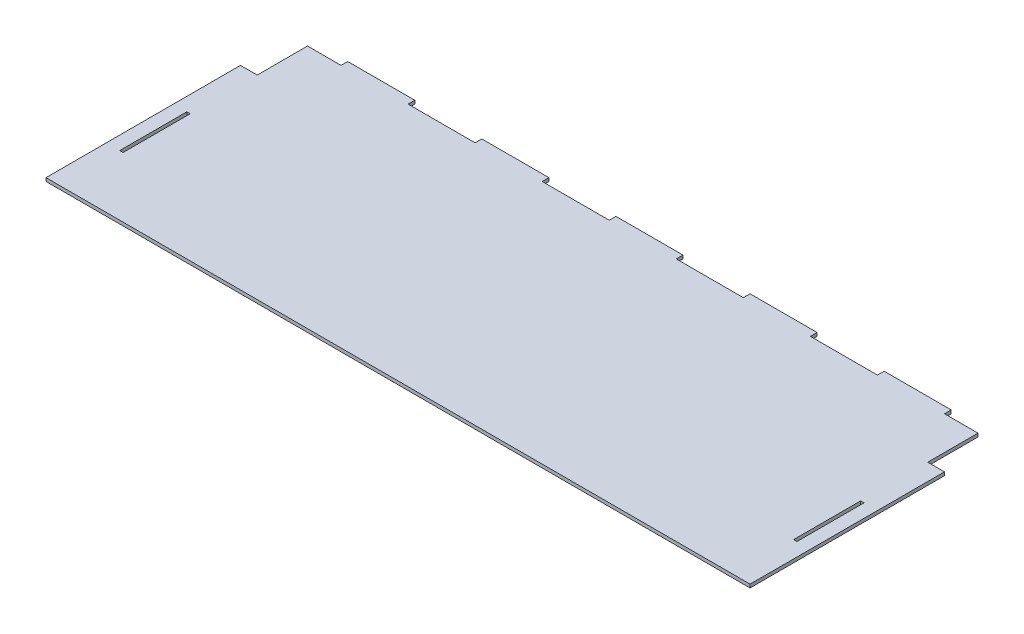
SolidWorks part; units mm, degrees
ref_plane "Přední rovina" through (0, 0, 0) normal (0, 0, 1) x (1, 0, 0)
ref_plane "Horní rovina" through (0, 0, 0) normal (0, 1, 0) x (1, 0, 0)
ref_plane "Pravá rovina" through (0, 0, 0) normal (1, 0, 0) x (0, 0, -1)
sketch "Skica1" plane through (0, 0, 0) normal (0, 1, 0) x (1, 0, 0)
  line L0 (100, 0) -> (100, 43.3055)
  line L5 (0, 0) -> (200, 0)
  line L6 (0, 0) -> (0, 73)
  line L7 (0, 73) -> (200, 73)
  line L8 (200, 0) -> (200, 73)
  line L9 (0, 58) -> (-5, 58)
  line L10 (0, 58) -> (0, 0)
  line L11 (0, 0) -> (-5, 0)
  line L12 (-5, 58) -> (-5, 0)
  line L13 (0, 38) -> (-1, 38)
  line L14 (0, 38) -> (0, 18)
  line L15 (0, 18) -> (-1, 18)
  line L16 (-1, 38) -> (-1, 18)
  line L17 (200, 18) -> (201, 18)
  line L18 (201, 38) -> (201, 18)
  line L19 (200, 38) -> (201, 38)
  line L20 (200, 38) -> (200, 18)
  line L21 (200, 0) -> (205, 0)
  line L22 (205, 58) -> (205, 0)
  line L23 (200, 58) -> (205, 58)
  line L24 (200, 58) -> (200, 0)
  line L25 (0, 0) -> (-5, 0)
  line L26 (10, 73) -> (30, 73)
  line L27 (10, 73) -> (10, 75)
  line L28 (10, 75) -> (30, 75)
  line L29 (30, 73) -> (30, 75)
  line L30 (50, 73) -> (70, 73)
  line L31 (50, 73) -> (50, 75)
  line L32 (50, 75) -> (70, 75)
  line L33 (70, 73) -> (70, 75)
  line L34 (90, 73) -> (110, 73)
  line L35 (90, 73) -> (90, 75)
  line L36 (90, 75) -> (110, 75)
  line L37 (110, 73) -> (110, 75)
  line L38 (130, 73) -> (150, 73)
  line L39 (130, 73) -> (130, 75)
  line L40 (130, 75) -> (150, 75)
  line L41 (150, 73) -> (150, 75)
  line L42 (170, 73) -> (190, 73)
  line L43 (170, 73) -> (170, 75)
  line L44 (170, 75) -> (190, 75)
  line L45 (190, 73) -> (190, 75)
  line L46 (205, 0) -> (200, 0)
  point P41 (50, 74)
  dimension "D1" = 200
  dimension "D2" = 73
  dimension "D3" = 15
  dimension "D4" = 5
  dimension "D5" = 1
  dimension "D6" = 20
  dimension "D7" = 20
  dimension "D8" = 10
  dimension "D9" = 20
  dimension "D10" = 20
  dimension "D11" = 20
  dimension "D12" = 20
  dimension "D13" = 20
  dimension "D14" = 20
  dimension "D15" = 20
  dimension "D16" = 20
  dimension "D17" = 20
  dimension "D18" = 2
extrude "Přidat vysunutím1" add sketch "Skica1" along normal blind 1 contours L16 L13 L10 L9 L12 L11 L6 L15 | L5 L8 L7 L6 L10 | L23 L8 L19 L18 L17 L21 L22 | L7 L45 L44 L43 | L7 L41 L40 L39 | L7 L37 L36 L35 | L7 L33 L32 L31 | L7 L29 L28 L27 region at (2.1291, 0, -9) region at (-2.6481, 0, -29.0741) region at (202.6481, 0, -29.0741) region at (20, 0, -74) region at (180, 0, -74) region at (60, 0, -74) region at (140, 0, -74) region at (100, 0, -74)
